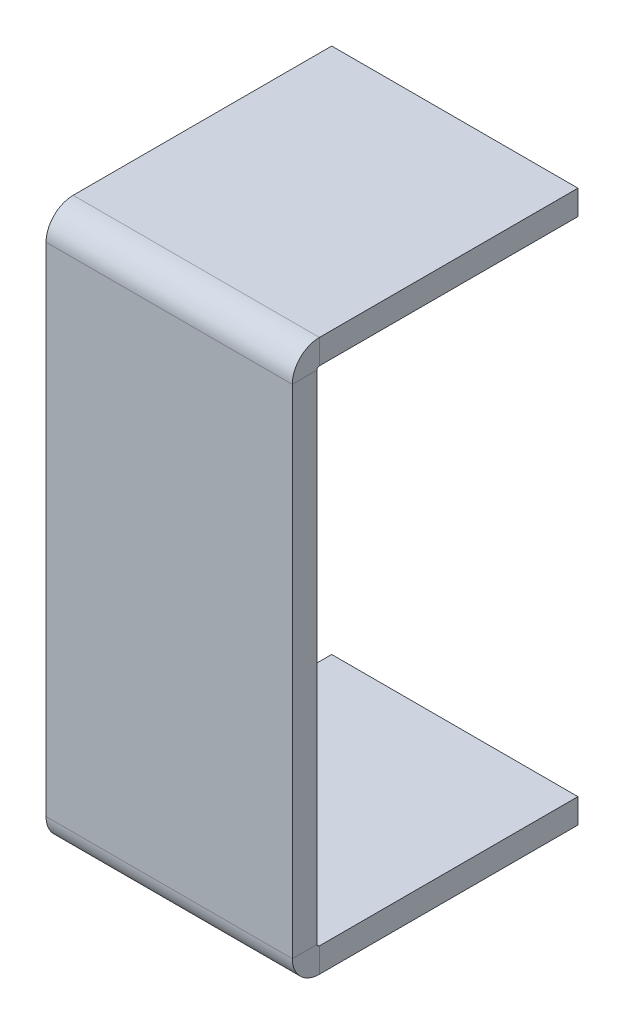
SolidWorks part; units mm, degrees
note: The reader was unsure of these and kept them because the rebuilt part matched: flange length of "边线-法兰1".
ref_plane "前视基准面" through (0, 0, 0) normal (0, 0, 1) x (1, 0, 0)
ref_plane "上视基准面" through (0, 0, 0) normal (0, 1, 0) x (1, 0, 0)
ref_plane "右视基准面" through (0, 0, 0) normal (1, 0, 0) x (0, 0, -1)
sketch "草图1" plane through (0, 0, 0) normal (0, 0, 1) x (1, 0, 0)
  line L1 (-50, 112) -> (50, 112)
  line L2 (-50, 112) -> (-50, -112)
  line L3 (-50, -112) -> (50, -112)
  line L4 (50, 112) -> (50, -112)
  line L5 (-50, 112) -> (50, -112) construction
  line L6 (-50, -112) -> (50, 112) construction
  point P0 (0, 0)
  dimension "D1" = 224
  dimension "D2" = 100
base flange "基体-法兰1" sketch "草图1" thickness 10 reverse thickness direction no parameters "D1"=1
edge flange "边线-法兰1" sketch "草图10" flange profiles "草图10", "草图11" flange angle 90 flange length 116 flange position material inside bend radius 1 thickness 10 relief rectangular parameters "D6"=10, "D8"=1
sketch "草图10" plane through (0, 112, -10) normal (0, -1, 0) x (-1, 0, 0)
  line L1 (50, 0) -> (-50, 0) construction
  line L2 (-50, 0) -> (-50, 106)
  line L3 (-50, 106) -> (50, 106)
  line L4 (50, 106) -> (50, 0)
  line L5 (50, 0) -> (-50, 0)
sketch "草图11" plane through (0, -112, -10) normal (0, 1, 0) x (1, 0, 0)
  line L0 (50, 0) -> (-50, 0) construction
  line L1 (50, 0) -> (-50, 0)
  line L2 (50, 0) -> (50, 106)
  line L3 (50, 106) -> (-50, 106)
  line L4 (-50, 106) -> (-50, 0)
bend "边线折弯1" bend radius 1 bend angle 90 parameters "D5"=1
bend "边线折弯2" bend radius 1 bend angle 90 parameters "D5"=2
sketch "折弯-线1" [suppressed] plane through (0, 0, 0) normal (0, 1, 0) x (1, 0, 0)
sketch "边界框1" [suppressed] plane through (0, 0, 0) normal (0, 1, 0) x (1, 0, 0)
sheet metal parameters "钣金6" thickness 10 parameters "D1"=1
flat pattern "平板型式6" [suppressed]
sketch "折弯-线2" plane through (0, 0, 0) normal (0, 1, 0) x (1, 0, 0)
sketch "边界框2" [suppressed] plane through (0, 0, 0) normal (0, 1, 0) x (1, 0, 0)
sheet metal parameters "钣金7" thickness 10 parameters "D1"=1
flat pattern "平板型式6"
sketch "折弯-线2" plane through (0, 0, 0) normal (0, 0, 1) x (1, 0, 0)
  line L0 (-50, -103.25) -> (50, -103.25) construction
  line L1 (50, 103.25) -> (-50, 103.25) construction
  line L2 (-50, -103.25) -> (50, -103.25) construction
  line L3 (50, 103.25) -> (-50, 103.25) construction
sketch3d "边界框2" [suppressed]
  line L0 (50, 210.5, 0) -> (50, -210.5, 0) construction
  line L1 (-50, 210.5, 0) -> (-50, -210.5, 0) construction
  line L2 (50, 210.5, 0) -> (-50, 210.5, 0) construction
  line L3 (50, -210.5, 0) -> (-50, -210.5, 0) construction
bend of the flat pattern "展开-<边线折弯1>1"
bend of the flat pattern "展开-<边线折弯2>1"
